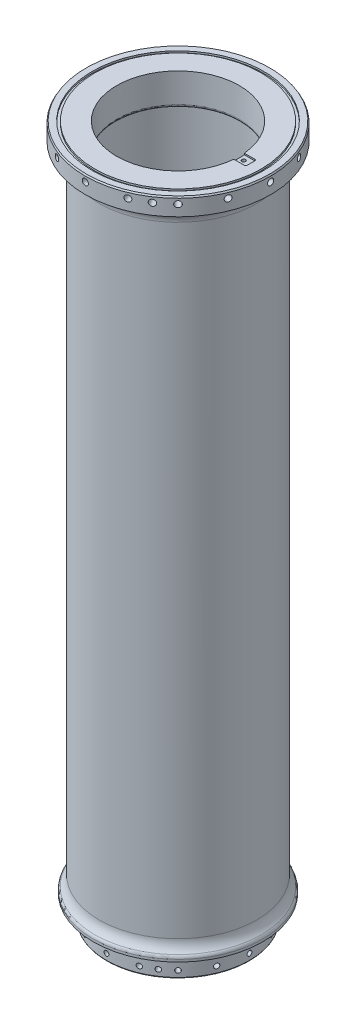
SolidWorks part; units mm, degrees
material "Cast Alloy Steel"
ref_plane "前视" through (0, 0, 0) normal (0, 0, 1) x (1, 0, 0)
ref_plane "上视" through (0, 0, 0) normal (0, 1, 0) x (1, 0, 0)
ref_plane "右视" through (0, 0, 0) normal (1, 0, 0) x (0, 0, -1)
sketch "草图1" plane through (0, 0, 0) normal (0, 0, 1) x (1, 0, 0)
  line L0 (0, 0) -> (0, -2.4756) construction
  line L1 (-42, 0) -> (-63.5, 0)
  line L2 (-63.5, 0) -> (-63.5, -12)
  line L3 (-63.5, -12) -> (-54, -12)
  line L4 (-58, -455) -> (-58, -458)
  line L5 (-49, -474) -> (-39.5, -474)
  line L6 (-58, -458) -> (-49, -458)
  line L7 (-42, 0) -> (-42, -22)
  line L8 (-49, -458) -> (-49, -474)
  line L9 (-42, -22) -> (-48, -22)
  line L10 (-48, -22) -> (-48, -451)
  line L11 (-48, -451) -> (-39.5, -451)
  line L12 (-39.5, -451) -> (-39.5, -474)
  line L13 (-58, -455) -> (-54, -455)
  line L14 (-54, -455) -> (-54, -12)
  dimension "D1" = 127
  dimension "D2" = 116
  dimension "D3" = 12
  dimension "D4" = 462
  dimension "D5" = 84
  dimension "D6" = 98
  dimension "D7" = 16
  dimension "D8" = 10
  dimension "D9" = 7
  dimension "D10" = 6
  dimension "D11" = 108
  dimension "D12" = 3
  dimension "D13" = 79
revolve "旋转1" add sketch "草图1" angle 360 about L0
ref_plane "基准面1" through (-63.5, 0, 0) normal (-1, 0, 0) x (0, 0, 1)
hole_wizard "M5 螺纹孔4" positions "草图6" profile "草图7" tap size "M5" standard "GB"
sketch "草图6" plane through (-63.5, 0, 0) normal (-1, 0, 0) x (0, 0, 1)
  point P0 (0, -4.5)
  dimension "D1" = 4.5
sketch "草图7" plane through (-63.5, -4.5, 0) normal (0, 1, 0) x (0, 0, 1)
  line L0 (0, 0) -> (0, 15.2618)
  line L1 (0, 15.2618) -> (2.1, 14)
  line L2 (2.1, 14) -> (2.1, 0)
  line L5 (2.1, 0) -> (0, 0)
  line L10 (0, 15.2618) -> (-2.1, 14) construction
  line L11 (0, -6.35) -> (0, 107.95) construction
  dimension "螺纹孔钻头直径" = 4.2
  dimension "螺纹孔钻头深度" = 14
  dimension "导头角度" = 118
cosmetic thread "孔螺蚊线2" parameters "D1"=13, "D2"=5
pattern_circular "阵列(圆周)1" count 16 over 360 about axis through (0, 0, 0) along (0, 1, 0) of "M5 螺纹孔4"
fillet "圆角1" radius 10 2 edges at (0, -455, 54) (0, -12, 54)
ref_plane "基准面2" through (-49, 0, 0) normal (-1, 0, 0) x (0, 0, 1)
hole_wizard "M4 螺纹孔1" positions "草图8" profile "草图9" tap size "M4" standard "GB"
sketch "草图8" plane through (-49, 0, 0) normal (-1, 0, 0) x (0, 0, 1)
  line L0 (-42, -474) -> (42, -474) construction
  point P0 (0, -469.3)
  dimension "D1" = 4.7
sketch "草图9" plane through (-49, -469.3, 0) normal (0, 1, 0) x (0, 0, 1)
  line L0 (0, 0) -> (0, 11.0914)
  line L1 (0, 11.0914) -> (1.65, 10.1)
  line L2 (1.65, 10.1) -> (1.65, 0)
  line L5 (1.65, 0) -> (0, 0)
  line L10 (0, 11.0914) -> (-1.65, 10.1) construction
  line L11 (0, -6.35) -> (0, 107.95) construction
  dimension "螺纹孔钻头直径" = 3.3
  dimension "螺纹孔钻头深度" = 10.1
  dimension "导头角度" = 118
cosmetic thread "孔螺蚊线3" parameters "D1"=8, "D2"=4
pattern_circular "阵列(圆周)2" count 16 over 360 about axis through (0, 0, 0) along (0, 1, 0) of "M4 螺纹孔1"
pattern_circular "阵列(圆周)3" count 2 over 123.75 about axis through (0, 0, 0) along (0, 1, 0) of "M4 螺纹孔1"
pattern_circular "阵列(圆周)4" count 2 over 123.75 about axis through (0, 0, 0) along (0, 1, 0) of "M4 螺纹孔1" reverse direction yes
fillet "圆角2" radius 2 4 edges at (0, -451, 39.5) (0, -22, 42) (0, -22, 48) (0, -451, 48)
fillet "圆角3" radius 3 1 edges at (0, -455, 58)
pattern_circular "阵列(圆周)5" count 2 over 123.75 about axis through (0, 0, 0) along (0, 1, 0) of "M5 螺纹孔4"
pattern_circular "阵列(圆周)6" count 2 over 123.75 about axis through (0, 0, 0) along (0, 1, 0) of "M5 螺纹孔4" reverse direction yes
sketch "草图12" plane through (0, 0, 0) normal (0, 1, 0) x (1, 0, 0)
  line L1 (50, -3.6) -> (26, -3.6)
  line L2 (50, -3.6) -> (50, 3.6)
  line L3 (50, 3.6) -> (26, 3.6)
  line L4 (26, -3.6) -> (26, 3.6)
  line L5 (50, -3.6) -> (26, 3.6) construction
  line L6 (50, 3.6) -> (26, -3.6) construction
  point P0 (38, 0)
  dimension "D1" = 38
  dimension "D2" = 12
  dimension "D3" = 7.2
extrude "切除-拉伸1" cut sketch "草图12" against normal blind 1
hole_wizard "M3 螺纹孔1" positions "草图10" profile "草图11" tap size "M3" standard "GB"
sketch "草图10" plane through (0, -1, 0) normal (0, 1, 0) x (1, 0, 0)
  point P0 (45, 0)
  dimension "D1" = 45
sketch "草图11" plane through (45, -1, 0) normal (1, 0, 0) x (0, 0, 1)
  line L0 (0, 0) -> (0, 8.2511)
  line L1 (0, 8.2511) -> (1.25, 7.5)
  line L2 (1.25, 7.5) -> (1.25, 0)
  line L5 (1.25, 0) -> (0, 0)
  line L10 (0, 8.2511) -> (-1.25, 7.5) construction
  line L11 (0, -6.35) -> (0, 107.95) construction
  dimension "螺纹孔钻头直径" = 2.5
  dimension "螺纹孔钻头深度" = 7.5
  dimension "导头角度" = 118
cosmetic thread "孔螺蚊线4" parameters "D1"=6, "D2"=3
fillet "圆角4" radius 1 2 edges at (50, -0.5, -3.6) (50, -0.5, 3.6)
sketch "草图13" plane through (0, -474, 0) normal (0, -1, 0) x (1, 0, 0)
  line L0 (44.4138, -12.505) -> (32.6444, -10.1639)
  line L1 (44.4138, -12.505) -> (45.8184, -5.4433)
  line L2 (32.6444, -10.1639) -> (34.049, -3.1022)
  line L3 (45.8184, -5.4433) -> (34.049, -3.1022)
  line L4 (44.4138, -12.505) -> (34.049, -3.1022) construction
  line L5 (32.6444, -10.1639) -> (45.8184, -5.4433) construction
  line L6 (39.2314, -7.8036) -> (0, 0) construction
  line L7 (0, 0) -> (95.5127, 0) construction
  point P1 (39.2314, -7.8036)
  dimension "D1" = 11.25
  dimension "D2" = 7.2
  dimension "D3" = 40
  dimension "D4" = 6
extrude "切除-拉伸2" cut sketch "草图13" against normal blind 5
fillet "圆角5" radius 1 2 edges at (45.8184, -471.5, -5.4433) (44.4138, -471.5, -12.505)
hole_wizard "M3 螺纹孔2" positions "草图14" profile "草图15" tap size "M3" standard "GB"
sketch "草图14" plane through (0, -469, 0) normal (0, -1, 0) x (-1, 0, 0)
  line L0 (0, 0) -> (-40.7007, 8.1056) construction
  line L2 (0, 0) -> (-67.6424, 0) construction
  point P0 (-40.7007, 8.1056)
  dimension "D1" = 11.263
  dimension "D2" = 41.5
sketch "草图15" plane through (40.7007, -469, -8.1056) normal (1, 0, 0) x (0, 0, -1)
  line L0 (0, 0) -> (0, 8.2511)
  line L1 (0, 8.2511) -> (1.25, 7.5)
  line L2 (1.25, 7.5) -> (1.25, 0)
  line L5 (1.25, 0) -> (0, 0)
  line L10 (0, 8.2511) -> (-1.25, 7.5) construction
  line L11 (0, -6.35) -> (0, 107.95) construction
  dimension "螺纹孔钻头直径" = 2.5
  dimension "螺纹孔钻头深度" = 7.5
  dimension "导头角度" = 118
cosmetic thread "孔螺蚊线5" parameters "D1"=6, "D2"=3
chamfer "倒角1" distance 1 angle 30 1 edges at (0, 0, 63.5) first distance on face at (36.96, -4.9817, -51.6354)
chamfer "倒角2" distance 0.3 angle 60 1 edges at (0, -474, 49) first distance on face at (29.7913, -474, -5.9259)
sketch "草图16" plane through (0, -474, 0) normal (0, -1, 0) x (1, 0, 0)
  circle A0 centre (0, 0) radius 45.85
  circle A1 centre (0, 0) radius 47.95
  dimension "D1" = 95.9
  dimension "D2" = 91.7
extrude "切除-拉伸3" cut sketch "草图16" against normal blind 1.2
sketch "草图17" plane through (0, 0, 0) normal (0, 1, 0) x (1, 0, 0)
  circle A0 centre (0, 0) radius 57.01
  circle A1 centre (0, 0) radius 58.81
  dimension "D1" = 114.02
  dimension "D2" = 1.8
extrude "切除-拉伸4" cut sketch "草图17" against normal blind 1.2
